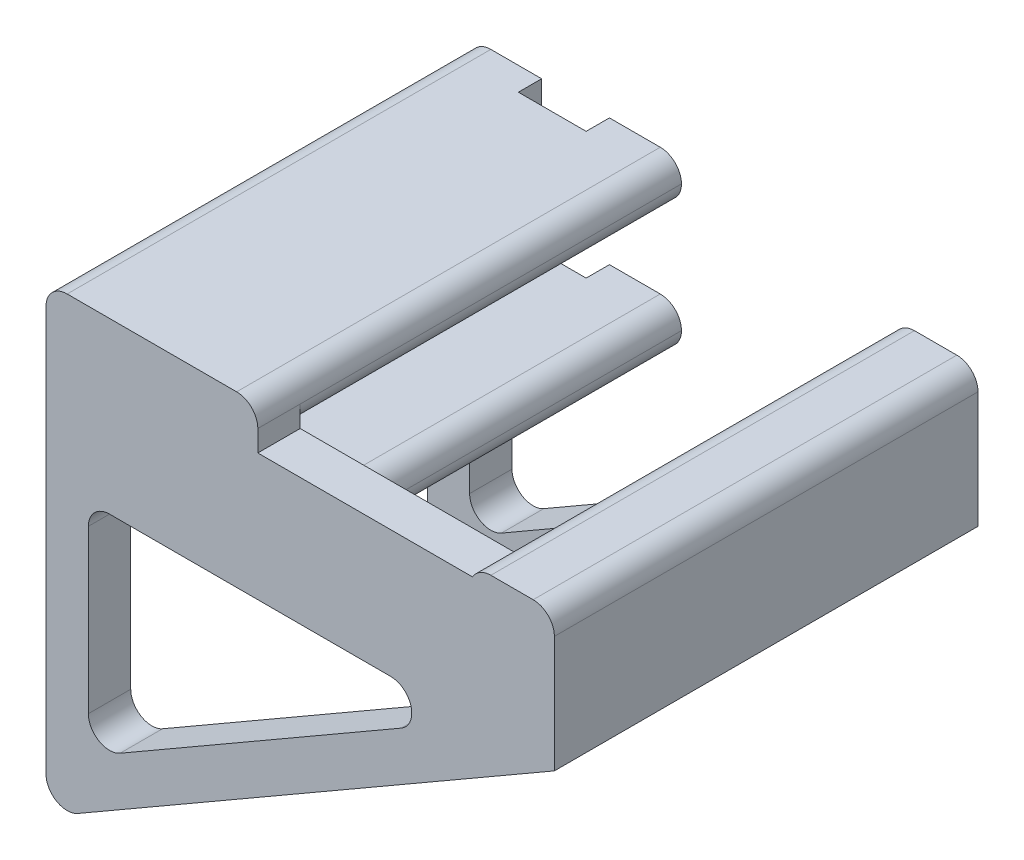
SolidWorks part; units mm, degrees
ref_plane "Front Plane" through (0, 0, 0) normal (0, 0, 1) x (1, 0, 0)
ref_plane "Top Plane" through (0, 0, 0) normal (0, 1, 0) x (1, 0, 0)
ref_plane "Right Plane" through (0, 0, 0) normal (1, 0, 0) x (0, 0, -1)
sketch "Sketch1" plane through (0, 0, 0) normal (0, 1, 0) x (1, 0, 0)
  line L1 (0, 0) -> (10, 0)
  line L2 (0, 0) -> (0, 18)
  line L3 (0, 18) -> (10, 18)
  line L4 (10, 0) -> (10, 18)
  dimension "D1" = 18
  dimension "D2" = 10
extrude "Extrude-Thin1" add sketch "Sketch1" along normal blind 2 thin thin type one direction wall 2
sketch "Sketch2" plane through (0, 2, 0) normal (0, 1, 0) x (1, 0, 0)
  line L0 (-2, -2) -> (12, -2) construction
  line L1 (12, 20) -> (10, 20)
  line L2 (12, 20) -> (12, -2)
  line L3 (12, -2) -> (10, -2)
  line L4 (10, 20) -> (10, -2)
extrude "Boss-Extrude1" add sketch "Sketch2" along normal blind 4.5
sketch "Sketch3" plane through (-2, 0, 0) normal (-1, 0, 0) x (0, 0, 1)
  line L6 (-20, 0) -> (2, 0)
  line L7 (-20, 0) -> (-20, 8)
  line L8 (-20, 8) -> (2, 8)
  line L9 (2, 0) -> (2, 8)
  dimension "D1" = 8
extrude "Extrude-Thin2" add sketch "Sketch3" against normal blind 2 thin thin type one direction reverse wall 2
sketch "Sketch4" plane through (12, 0, 0) normal (1, 0, 0) x (0, 0, -1)
  line L1 (20, 0) -> (18, 0)
  line L2 (20, 0) -> (20, 10.0769)
  line L3 (20, 10.0769) -> (18, 10.0769)
  line L4 (18, 0) -> (18, 10.0769)
  dimension "D1" = 2
extrude "Cut-Extrude1" cut sketch "Sketch4" against normal through all
sketch "Sketch5" plane through (0, 0, -18) normal (0, 0, -1) x (-1, 0, 0)
  line L0 (-12, 6.5) -> (-12, 0) construction
  line L1 (-12, 5.1) -> (-10.9, 5.1)
  line L2 (-12, 5.1) -> (-12, 0.9)
  line L3 (-12, 0.9) -> (-10.9, 0.9)
  line L4 (-10.9, 5.1) -> (-10.9, 0.9)
  line L5 (-10, 0) -> (-12, 0) construction
  line L6 (0, 6) -> (2, 6) construction
  line L7 (2, 8) -> (0.9, 8)
  line L8 (2, 8) -> (2, 6)
  line L9 (2, 6) -> (0.9, 6)
  line L10 (0.9, 8) -> (0.9, 6)
  line L11 (2, 0) -> (0, 0) construction
  line L12 (2, 2) -> (0.9, 2)
  line L13 (2, 2) -> (2, 0)
  line L14 (2, 0) -> (0.9, 0)
  line L15 (0.9, 2) -> (0.9, 0)
  line L16 (-12, 3) -> (-10.9, 3) construction
  dimension "D1" = 1.1
  dimension "D2" = 4.2
  dimension "D3" = 0.9
  dimension "D4" = 1.1
  dimension "D5" = 1.1
extrude "Cut-Extrude2" cut sketch "Sketch5" against normal blind 1.1 contours L2 L1 L4 L3 | L13 L12 L15 L14 | L8 L7 L10 L9
sketch "Sketch6" plane through (-2, 0, 0) normal (-1, 0, 0) x (0, 0, 1)
  line L8 (-16.9, 2) -> (-16.9, 0)
  line L9 (-16.9, 0) -> (2, 0)
  line L10 (2, 0) -> (2, 8)
  line L11 (2, 8) -> (-16.9, 8)
  line L12 (-16.9, 8) -> (-16.9, 6)
  line L13 (-16.9, 6) -> (0, 6)
  line L14 (0, 6) -> (0, 2)
  line L15 (0, 2) -> (-16.9, 2)
  line L16 (-16.9, 2) -> (-16.9, 0)
  line L17 (-16.9, 0) -> (2, 0)
  line L18 (2, 0) -> (2, 8)
  line L19 (2, 8) -> (-16.9, 8)
  line L20 (-16.9, 8) -> (-16.9, 6)
  line L21 (-16.9, 6) -> (0, 6)
  line L22 (0, 6) -> (0, 2)
  line L23 (0, 2) -> (-16.9, 2)
  dimension "D1" = 0
extrude "Boss-Extrude2" add sketch "Sketch6" along normal blind 8
sketch "Sketch7" plane through (0, 8, 0) normal (0, 1, 0) x (1, 0, 0)
  line L0 (-5, -2) -> (-5, 16.9) construction
  line L1 (0, -2) -> (-10, -2) construction
  line L2 (-10, 16.9) -> (-0.9, 16.9) construction
  line L3 (-10, 18) -> (-9.1, 18)
  line L4 (-9.1, 18) -> (-9.1, 16.9)
  line L5 (-10, 16.9) -> (-10, 18)
  line L6 (-9.1, 18) -> (-6.6, 18)
  line L7 (-0.9, 16.9) -> (-3.4, 16.9)
  line L8 (-0.9, 16.9) -> (-0.9, 18)
  line L9 (-0.9, 18) -> (-0.9, 16.9)
  line L10 (-0.9, 16.9) -> (-10, 16.9)
  line L11 (-10, 16.9) -> (-10, -2)
  line L12 (-10, -2) -> (0, -2)
  line L13 (0, -2) -> (0, 18)
  line L14 (0, 18) -> (-0.9, 18)
  line L15 (-0.9, 18) -> (-0.9, 16.9)
  line L16 (-0.9, 16.9) -> (-10, 16.9)
  line L17 (-10, 16.9) -> (-10, -2)
  line L18 (-10, -2) -> (0, -2)
  line L19 (0, -2) -> (0, 18)
  line L20 (0, 18) -> (-0.9, 18)
  line L21 (-0.9, 18) -> (-3.4, 18)
  line L22 (-3.4, 16.9) -> (-3.4, 18)
  line L23 (-6.6, 16.9) -> (-6.6, 18)
  line L24 (-9.1, 16.9) -> (-6.6, 16.9)
  line L25 (-9.1, 16.9) -> (-9.1, 18)
  line M12 (-0.9, 18) -> (-0.9, 16.9)
  line M13 (-0.9, 16.9) -> (-10, 16.9)
  dimension "D2" = 2.5
  dimension "D1" = 0
extrude "Boss-Extrude3" add sketch "Sketch7" against normal through all contours L22 L21 M13 M12 | L16 L23 L6 L4 | L5 L4 L3 M13 region at (-9.55, 8, -17.45) region at (-7.85, 8, -17.45) region at (-2.15, 8, -17.45)
sketch "Sketch8" plane through (0, 0, -18) normal (0, 0, -1) x (-1, 0, 0)
  line L0 (0.9, 6) -> (10, 6)
  line L1 (10, 6) -> (0.9, 2)
  line L2 (0.9, 2) -> (10, 2)
  line L3 (10, 2) -> (10, 6)
  line L4 (0.9, 6) -> (0.9, 2)
  line M2 (6.6, 8) -> (6.6, 0)
  line M4 (10, 0) -> (10, 8)
extrude "Cut-Extrude3" cut sketch "Sketch8" against normal blind 1.1 contours L0 L4 L1 M2 | L1 L2 M2 | L2 L1 M2 M4 | L1 L0 M2 region at (-3.3168, 4.5312, -18) region at (-7.7333, 5.5018, -18) region at (-4.7, 2.8352, -18) region at (-8.4302, 3.655, -18)
sketch "Sketch9" plane through (0, 0, 0) normal (1, 0, 0) x (0, 0, -1)
  line L1 (0, 2) -> (-2, 2)
  line L2 (0, 2) -> (0, 6)
  line L3 (0, 6) -> (-2, 6)
  line L4 (-2, 2) -> (-2, 6)
  line L6 (0, 6) -> (18, 6)
  line L7 (18, 6) -> (18, 8)
  line L8 (18, 8) -> (-2, 8)
  line L9 (-2, 8) -> (-2, 2)
  line L10 (-2, 2) -> (0, 2)
  line L11 (0, 2) -> (0, 6)
  line L12 (0, 6) -> (18, 6)
  line L13 (18, 6) -> (18, 8)
  line L14 (18, 8) -> (-2, 8)
  line L15 (-2, 8) -> (-2, 2)
  line L16 (-2, 2) -> (0, 2)
  line L17 (0, 2) -> (0, 6)
  line M11 (-2, 8) -> (-2, 2)
  line M12 (-2, 2) -> (0, 2)
  line M13 (0, 2) -> (0, 6)
  dimension "D2" = 4
  dimension "D1" = 0
extrude "Boss-Extrude4" add sketch "Sketch9" along normal through all contours L3 M13 M11 M12 region at (0, 4, 1)
sketch "Sketch10" plane through (12, 0, 0) normal (1, 0, 0) x (0, 0, -1)
  line L8 (-2, 6.5) -> (-2, 0)
  line L9 (-2, 0) -> (18, 0)
  line L10 (18, 0) -> (18, 0.9)
  line L11 (18, 0.9) -> (16.9, 0.9)
  line L12 (16.9, 0.9) -> (16.9, 5.1)
  line L13 (16.9, 5.1) -> (18, 5.1)
  line L14 (18, 5.1) -> (18, 6.5)
  line L15 (18, 6.5) -> (-2, 6.5)
  line L16 (-2, 6.5) -> (-2, 0)
  line L17 (-2, 0) -> (18, 0)
  line L18 (18, 0) -> (18, 0.9)
  line L19 (18, 0.9) -> (16.9, 0.9)
  line L20 (16.9, 0.9) -> (16.9, 5.1)
  line L21 (16.9, 5.1) -> (18, 5.1)
  line L22 (18, 5.1) -> (18, 6.5)
  line L23 (18, 6.5) -> (-2, 6.5)
  dimension "D1" = 0
extrude "Boss-Extrude5" add sketch "Sketch10" along normal blind 2
sketch "Sketch11" plane through (0, 0, -16.9) normal (0, 0, -1) x (-1, 0, 0)
  line L0 (-14, 0.9) -> (-10.9, 0.9) construction
  line L1 (-14, 5.1) -> (-13.1, 5.1)
  line L2 (-14, 5.1) -> (-14, 0.9)
  line L3 (-14, 0.9) -> (-13.1, 0.9)
  line L4 (-13.1, 5.1) -> (-13.1, 0.9)
  line L5 (-10.9, 5.1) -> (-10.9, 0.9) construction
  dimension "D1" = 2.2
extrude "Boss-Extrude6" add sketch "Sketch11" along normal blind 1.1 contours L2 L1 L4 L3
sketch "Sketch12" plane through (0, 0, 2) normal (0, 0, 1) x (1, 0, 0)
  line L1 (-10, 0) -> (-5, 0)
  line L2 (-5, -10.9697) -> (-10, -13.8564)
  line L3 (-5, -10.9697) -> (14, 0)
  line L4 (-10, 0) -> (14, 0) construction
  line L5 (-10, -13.8564) -> (-10, 0)
  dimension "D1" = 30
sketch "Sketch13" plane through (0, 0, 2) normal (0, 0, 1) x (1, 0, 0)
  line L0 (-10, 0) -> (-10, -13.8564)
  line L2 (-10, -13.8564) -> (14, 0)
extrude "Extrude-Thin4" add sketch "Sketch13" against normal blind 2 thin thin type one direction reverse wall 2
pattern_linear "LPattern1" count 2 spacing 18 along (0, 0, -1) of "Extrude-Thin4"
sketch "Sketch14" plane through (0, 0, -16.9) normal (0, 0, -1) x (-1, 0, 0)
  line L1 (-10.9, 5.1) -> (-13.1, 5.1)
  line L2 (-10.9, 5.1) -> (-10.9, 0.9)
  line L3 (-10.9, 0.9) -> (-13.1, 0.9)
  line L4 (-13.1, 5.1) -> (-13.1, 0.9)
extrude "Cut-Extrude4" cut sketch "Sketch14" along normal blind 2
fillet "Fillet1" radius 1 18 edges at (0, 0, -9) (0, 2, -9) (10, 6.5, -8) (14, 6.5, -8) (0, 6, -9) (0, 8, -8) (-10, 8, -8) (-10, 6, -9) (-10, 0, -8) (-10, 2, -9) (10, 0, -17) (-8, 0, -17) (-8, -10.3923, -17) (-8, -10.3923, 1) (-8, 0, 1) (10, 0, 1) (-10, -13.8564, 1) (-10, -13.8564, -17)
